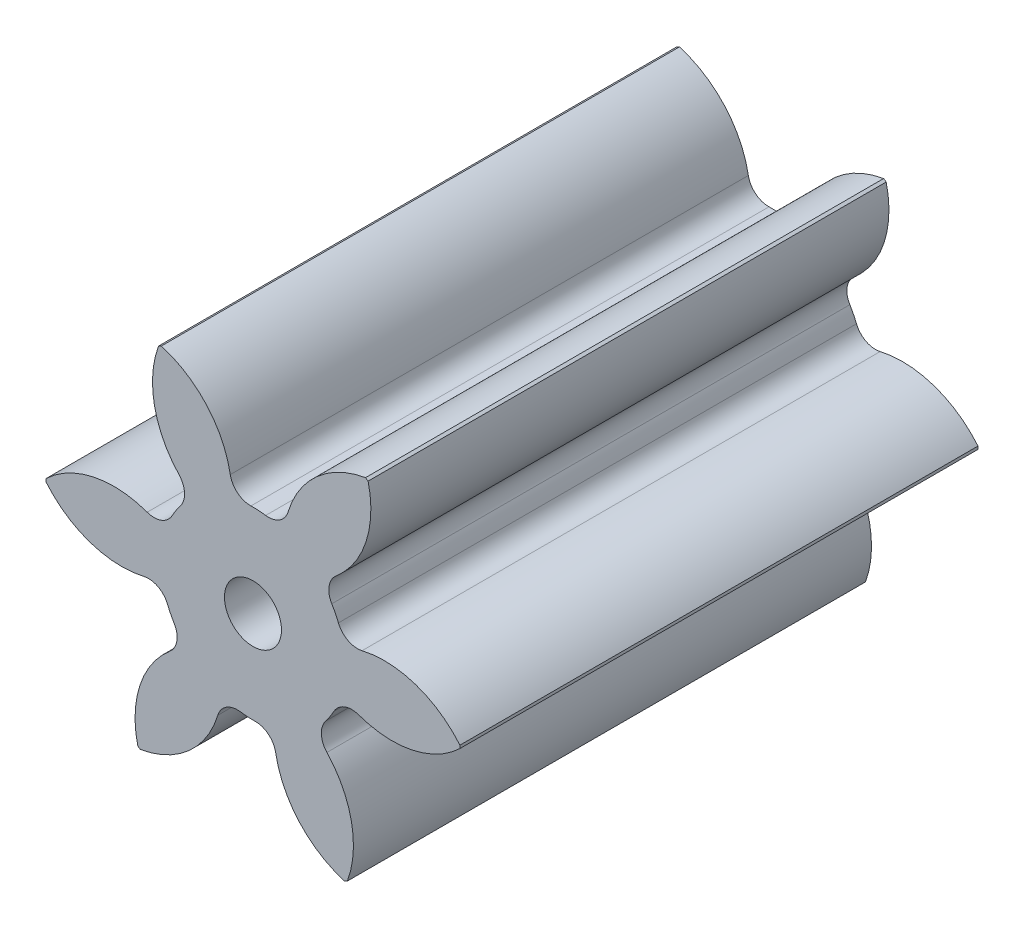
SolidWorks part; units mm, degrees
ref_plane "Front" through (0, 0, 0) normal (0, 0, 1) x (1, 0, 0)
ref_plane "Top" through (0, 0, 0) normal (0, 1, 0) x (1, 0, 0)
ref_plane "Right" through (0, 0, 0) normal (1, 0, 0) x (0, 0, -1)
sketch "Sketch3" plane through (0, 0, 0) normal (0, 0, 1) x (1, 0, 0)
  circle A0 centre (0, 0) radius 10.16
  dimension "od" = 20.32
extrude "gearBody" add sketch "Sketch3" along normal blind 25.4
sketch "Sketch2" plane through (0, 0, 0) normal (0, 0, 1) x (1, 0, 0)
  line L0 (0, 0) -> (6.8157, 2.8232) construction
  line L1 (3.4575, -10.8399) -> (0, 0) construction
  line L2 (0, 0) -> (36.3143, 0) construction
  line L3 (7.3626, -1.964) -> (4.7199, -5.9822) construction
  line L5 (6.0412, -3.9731) -> (0, 0) construction
  line L7 (0, 0) -> (7.3773, 0) construction
  arc A0 (7.1048, -1.9864) -> (4.6384, -5.7367) centre (0, 0) ccw construction
  arc A1 (10.1381, -0.6664) -> (4.628, -9.0447) centre (0, 0) ccw construction
  arc A2 (7.3626, -1.964) -> (4.7199, -5.9822) centre (0, 0) ccw construction
  arc A3 (3.566, -2.7793) -> (3.9646, -2.1733) centre (0, 0) ccw
  arc A4 (3.4575, -10.8399) -> (3.6251, -4.0834) centre (0.1078, -7.3765) ccw
  arc A5 (3.4575, -10.8399) -> (11.3227, 1.1195) centre (0, 0) ccw
  arc A6 (11.3227, 1.1195) -> (5.1854, -1.7109) centre (6.8157, 2.8232) cw
  arc A7 (3.9646, -2.1733) -> (5.1854, -1.7109) centre (4.8455, -2.6562) cw
  arc A8 (3.6251, -4.0834) -> (3.566, -2.7793) centre (4.3584, -3.3969) cw
  point P6 (11.3227, 1.1195)
  point P22 (3.4575, -10.8399)
  dimension "baseDia" = 14.7546
  dimension "od" = 20.32
  dimension "pd" = 15.24
  dimension "rd" = 9.0424
  dimension "rFillet" = 1.0046
  dimension "pointX" = 11.3227
  dimension "pointY" = 1.1195
  dimension "CTT" = 4.0183
  dimension "flankCenterAngle" = 22.5
extrude "toothCut" cut sketch "Sketch2" along normal through all
pattern_circular "CirPattern1" count 6 over 360 about axis through (0, 0, 25.4) along (0, 0, -1) of "toothCut"
ref_axis "toothSpace" through (0, 0, 0) along (0.8355, -0.5495, 0)
ref_axis "Axis2" through (4.5601, -9.0792, 0) along (-0.4488, 0.8936, 0)
sketch "hub1Dia" plane through (0, 0, 0) normal (0, 0, -1) x (-1, 0, 0)
  circle A0 centre (0, 0) radius 12.7
  dimension "hub1Dia" = 25.4
sketch "hub2Dia" plane through (0, 0, 25.4) normal (0, 0, 1) x (1, 0, 0)
  circle A0 centre (0, 0) radius 12.7
  dimension "hub2dia" = 25.4
sketch "boreDia" plane through (0, 0, 0) normal (0, 0, 1) x (1, 0, 0)
  circle A0 centre (0, 0) radius 1.397
  dimension "boreDia" = 2.794
extrude "bore" cut sketch "boreDia" against normal mid plane 25400
sketch "kwy1sketch" plane through (0, 0, 0) normal (0, 0, 1) x (1, 0, 0)
  line L0 (-2.3856, 3.2042) -> (0, 0) construction
  line L1 (26.1895, -13.9098) -> (5.816, -29.0782)
  line L2 (5.816, -29.0782) -> (-13.1446, -3.6114)
  line L3 (26.1895, -13.9098) -> (7.2289, 11.5571)
  line L4 (-13.1446, -3.6114) -> (0, 0)
  line L5 (0, 0) -> (7.2289, 11.5571)
  line L6 (0, 0) -> (3.7775, -2.4843) construction
  line L7 (16.0027, -21.494) -> (0, 0) construction
  arc A7 (3.566, -2.7793) -> (3.9646, -2.1733) centre (0, 0) ccw construction
  point P9 (16.0027, -21.494)
  point P13 (-0.3979, 0.5345)
  dimension "kwy1width" = 25.4
  dimension "kwy1depth" = 26.797
  dimension "kwy1angle" = 20
  dimension "kwy1Depth2" = 31.75
sketch "kwy2sketch" plane through (0, 0, 0) normal (0, 0, 1) x (1, 0, 0)
  line L0 (3.7775, -2.4843) -> (0, 0) construction
  line L1 (0, 0) -> (-2.7313, 0.4) construction
  line L2 (28.3544, 8.6831) -> (24.674, -16.4489)
  line L3 (24.674, -16.4489) -> (-6.741, -11.8483)
  line L4 (28.3544, 8.6831) -> (-3.0605, 13.2837)
  line L5 (-6.741, -11.8483) -> (0, 0)
  line L6 (0, 0) -> (-3.0605, 13.2837)
  arc A2 (3.566, -2.7793) -> (3.9646, -2.1733) centre (0, 0) ccw construction
  point P10 (26.5142, -3.8829)
  dimension "kwy2angle" = 25
  dimension "kwy2Width" = 25.4
  dimension "kwy2depth" = 26.797
  dimension "kwy2Depth2" = 31.75
sketch "kwy3sketch" plane through (0, 0, 0) normal (0, 0, 1) x (1, 0, 0)
  line L0 (3.7775, -2.4843) -> (0, 0) construction
  line L1 (0, 0) -> (-1.6019, -1.1926) construction
  line L2 (13.9098, 26.1895) -> (29.0782, 5.816)
  line L3 (29.0782, 5.816) -> (3.6114, -13.1446)
  line L4 (13.9098, 26.1895) -> (-11.5571, 7.2289)
  line L5 (3.6114, -13.1446) -> (0, 0)
  line L6 (-11.5571, 7.2289) -> (0, 0)
  point P10 (21.494, 16.0027)
  dimension "kwy3angle" = 70
  dimension "kwy3depth" = 26.797
  dimension "kwy3width" = 25.4
  dimension "kwy3Depth2" = 31.75
sketch "kwy4sketch" plane through (0, 0, 0) normal (0, 0, 1) x (1, 0, 0)
  line L0 (3.7775, -2.4843) -> (0, 0) construction
  line L1 (0, 0) -> (-0.2263, -1.545) construction
  line L2 (16.4489, 24.674) -> (-8.6831, 28.3544)
  line L3 (-8.6831, 28.3544) -> (-13.2837, -3.0605)
  line L4 (-13.2837, -3.0605) -> (0, 0)
  line L5 (11.8483, -6.741) -> (0, 0)
  line L6 (16.4489, 24.674) -> (11.8483, -6.741)
  point P15 (3.8829, 26.5142)
  dimension "kwy4angle" = 115
  dimension "kwy4depth" = 26.797
  dimension "kwy4width" = 25.4
  dimension "kwy4Depth2" = 31.75
sketch "kwy5sketch" plane through (0, 0, 0) normal (0, 0, 1) x (1, 0, 0)
  line L0 (3.7775, -2.4843) -> (0, 0) construction
  line L1 (0, 0) -> (0.8009, -1.0757) construction
  line L2 (-5.816, 29.0782) -> (-26.1895, 13.9098)
  line L3 (-26.1895, 13.9098) -> (-7.2289, -11.5571)
  line L4 (-5.816, 29.0782) -> (13.1446, 3.6114)
  line L5 (-7.2289, -11.5571) -> (0, 0)
  line L6 (13.1446, 3.6114) -> (0, 0)
  point P10 (-16.0027, 21.494)
  dimension "kwy5width" = 25.4
  dimension "kwy5depth" = 26.797
  dimension "kwy5angle" = 160
  dimension "kwy5Depth2" = 31.75
sketch "kwy6sketch" plane through (0, 0, 0) normal (0, 0, 1) x (1, 0, 0)
  line L0 (3.7775, -2.4843) -> (0, 0) construction
  line L1 (0, 0) -> (1.3259, -0.1942) construction
  line L2 (-24.674, 16.4489) -> (-28.3544, -8.6831)
  line L3 (-28.3544, -8.6831) -> (3.0605, -13.2837)
  line L4 (-24.674, 16.4489) -> (6.741, 11.8483)
  line L5 (3.0605, -13.2837) -> (0, 0)
  line L6 (6.741, 11.8483) -> (0, 0)
  point P10 (-26.5142, 3.8829)
  dimension "kwy6angle" = 205
  dimension "kwy6width" = 25.4
  dimension "kwy6depth" = 26.797
  dimension "kwy6Depth2" = 31.75
sketch "kwy7sketch" plane through (0, 0, 0) normal (0, 0, 1) x (1, 0, 0)
  line L0 (3.7775, -2.4843) -> (0, 0) construction
  line L1 (0, 0) -> (1.2042, 0.8965) construction
  line L2 (-29.0782, -5.816) -> (-13.9098, -26.1895)
  line L3 (-29.0782, -5.816) -> (-3.6114, 13.1446)
  line L4 (-13.9098, -26.1895) -> (11.5571, -7.2289)
  line L5 (-3.6114, 13.1446) -> (0, 0)
  line L6 (11.5571, -7.2289) -> (0, 0)
  point P10 (-21.494, -16.0027)
  dimension "kwy7angle" = 70
  dimension "kwy7width" = 25.4
  dimension "kwy7depth" = 26.797
  dimension "kwy7angle1" = 250
  dimension "kwy7Depth2" = 31.75
sketch "kwy8sketch" plane through (0, 0, 0) normal (0, 0, 1) x (1, 0, 0)
  line L0 (3.7775, -2.4843) -> (0, 0) construction
  line L1 (0, 0) -> (0.1933, 1.3197) construction
  line L2 (-16.4489, -24.674) -> (8.6831, -28.3544)
  line L3 (8.6831, -28.3544) -> (13.2837, 3.0605)
  line L4 (-16.4489, -24.674) -> (-11.8483, 6.741)
  line L5 (13.2837, 3.0605) -> (0, 0)
  line L6 (-11.8483, 6.741) -> (0, 0)
  point P10 (-3.8829, -26.5142)
  dimension "kwy8angle" = 295
  dimension "kwy8width" = 25.4
  dimension "kwy8depth" = 26.797
  dimension "kwy8Depth2" = 31.75
sketch "centerLine" plane through (0, 0, 0) normal (0, 1, 0) x (1, 0, 0)
  line L0 (0, 36.4807) -> (0, -59.6309) construction
ref_plane "CB1plane" through (0, 0, 0) normal (0, 0, -1) x (-1, 0, 0)
sketch "CB1diameter" plane through (0, 0, 0) normal (0, 0, -1) x (-1, 0, 0)
  circle A0 centre (0, 0) radius 12.7
  dimension "CB1diameter" = 25.4
ref_plane "CB2plane" through (0, 0, 25.4) normal (0, 0, 1) x (1, 0, 0)
sketch "CB2diameter" plane through (0, 0, 25.4) normal (0, 0, 1) x (1, 0, 0)
  circle A0 centre (0, 0) radius 12.7
  dimension "CB2diameter" = 25.4
ref_axis "Axis1" through (0, 0, 50) along (0, 0, -1)
sketch3d "3DSketch1" plane through (0, 0, 0) normal (0, 0, 1) x (1, 0, 0)
